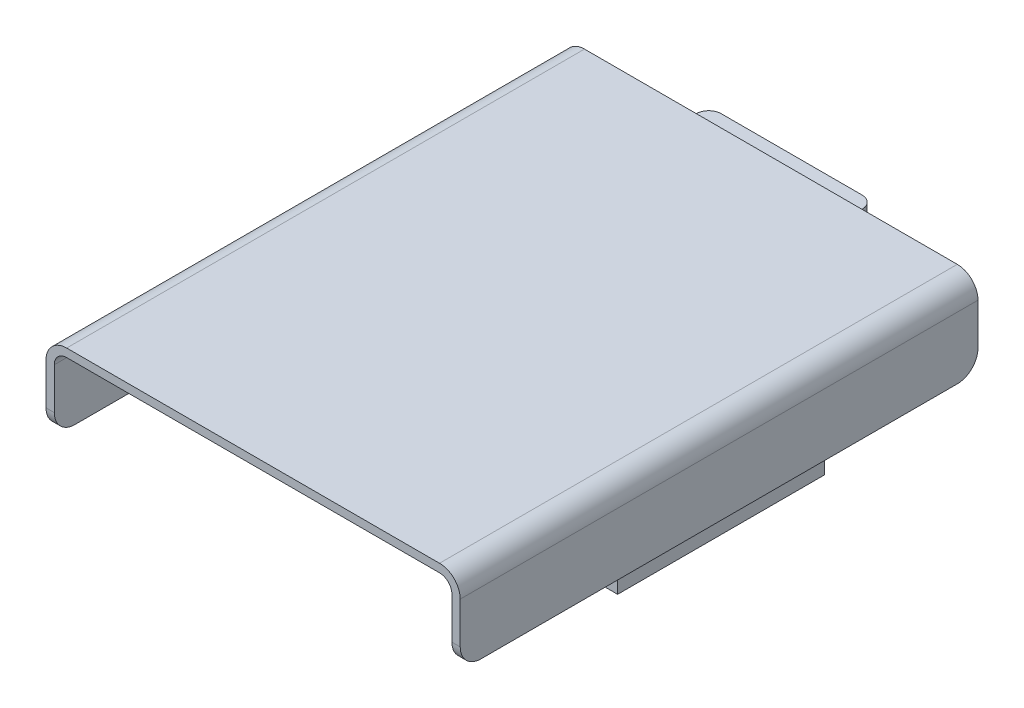
SolidWorks part; units mm, degrees
material "ABS"
ref_plane "Front Plane" through (0, 0, 0) normal (0, 0, 1) x (1, 0, 0)
ref_plane "Top Plane" through (0, 0, 0) normal (0, 1, 0) x (1, 0, 0)
ref_plane "Right Plane" through (0, 0, 0) normal (1, 0, 0) x (0, 0, -1)
sketch "Sketch1" plane through (0, 0, 0) normal (0, 0, 1) x (1, 0, 0)
  line L0 (-62.3906, 20.6479) -> (-62.3906, 26.5485) construction
  line L1 (-62.3906, 20.6479) -> (-62.3906, -14.3521) construction
  line L2 (-14.3906, 5.6479) -> (-14.3906, 20.6479)
  line L4 (-17.3906, 23.6479) -> (-107.3906, 23.6479)
  line L5 (-110.3906, 20.6479) -> (-110.3906, 5.6479)
  line L6 (-110.3906, 5.6479) -> (-112.3906, 5.6479)
  line L7 (-14.3906, 5.6479) -> (-12.3906, 5.6479)
  line L16 (-17.3906, 25.6479) -> (-107.3906, 25.6479)
  line L17 (-112.3906, 20.6479) -> (-112.3906, 5.6479)
  line L23 (-12.3906, 5.6479) -> (-12.3906, 20.6479)
  arc A0 (-107.3906, 25.6479) -> (-112.3906, 20.6479) centre (-107.3906, 20.6479) ccw
  arc A1 (-17.3906, 25.6479) -> (-12.3906, 20.6479) centre (-17.3906, 20.6479) cw
  arc A2 (-17.3906, 23.6479) -> (-14.3906, 20.6479) centre (-17.3906, 20.6479) cw
  arc A3 (-107.3906, 23.6479) -> (-110.3906, 20.6479) centre (-107.3906, 20.6479) ccw
  dimension "D4" = 20
  dimension "D5" = 100
  dimension "D1" = 5
  dimension "D2" = 2
  dimension "D3" = 20
extrude "Boss-Extrude1" add sketch "Sketch1" along normal blind 125
fillet "Fillet1" radius 5 4 edges at (-13.3906, 5.6479, 125) (-13.3906, 5.6479, 0) (-111.3906, 5.6479, 0) (-111.3906, 5.6479, 125)
sketch "Sketch2" plane through (0, 5.6479, 0) normal (0, -1, 0) x (1, 0, 0)
  line L1 (-107.3906, 35) -> (-110.3906, 35)
  line L2 (-107.3906, 35) -> (-107.3906, 85)
  line L3 (-107.3906, 85) -> (-110.3906, 85)
  line L4 (-110.3906, 35) -> (-110.3906, 85)
  line L6 (-82.3535, 85) -> (-110.3906, 85) construction
  line L7 (-110.3906, 120) -> (-110.3906, 5) construction
  line L9 (-12.3906, 35) -> (-12.3906, 85) construction
  line L10 (-15.3906, 85) -> (-12.3906, 85) construction
  line L11 (-15.3906, 35) -> (-15.3906, 85) construction
  line L12 (-15.3906, 35) -> (-12.3906, 35) construction
  point P5 (0, 0)
extrude "Boss-Extrude2" add sketch "Sketch2" against normal up to surface and the other way blind 5 up to face at (-109.2012, 22.4586, 62.5)
sketch "Sketch12" plane through (0, 5.6479, 0) normal (0, -1, 0) x (1, 0, 0)
  line L0 (-62.3906, 125) -> (-62.3906, 0) construction
  line L1 (-107.3906, 125) -> (-17.3906, 125) construction
  line L2 (-107.3906, 0) -> (-17.3906, 0) construction
  line L3 (-14.3906, 35) -> (-17.3906, 35)
  line L4 (-107.3906, 35) -> (-107.3906, 85)
  line L5 (-107.3906, 85) -> (-110.3906, 85)
  line L6 (-110.3906, 85) -> (-110.3906, 35)
  line L7 (-110.3906, 35) -> (-107.3906, 35)
  line L8 (-107.3906, 35) -> (-107.3906, 85) construction
  line L9 (-107.3906, 85) -> (-110.3906, 85) construction
  line L10 (-110.3906, 85) -> (-110.3906, 35) construction
  line L11 (-110.3906, 35) -> (-107.3906, 35) construction
  line L12 (-14.3906, 85) -> (-14.3906, 35)
  line L13 (-17.3906, 85) -> (-14.3906, 85)
  line L14 (-17.3906, 35) -> (-17.3906, 85)
  dimension "D1" = 0
extrude "Boss-Extrude5" add sketch "Sketch12" against normal up to surface and the other way blind 5 up to face at (-15.5799, 22.4586, 62.5)
sketch "Sketch3" plane through (0, 23.6479, 0) normal (0, -1, 0) x (1, 0, 0)
  line L0 (-62.3906, 0) -> (-62.3906, 120) construction
  line L1 (-42.3906, 10) -> (-82.3906, 10)
  line L2 (-42.3906, 10) -> (-42.3906, -5)
  line L3 (-42.3906, -5) -> (-82.3906, -5)
  line L4 (-82.3906, 10) -> (-82.3906, -5)
  line L5 (-62.3906, 125) -> (-62.3906, 127.9312) construction
  line L6 (-12.3906, 0) -> (-12.3906, 5) construction
  line L7 (-107.3906, 125) -> (-17.3906, 125) construction
  dimension "D1" = 20
  dimension "D2" = 40
  dimension "D3" = 15
  dimension "D4" = 50
extrude "Boss-Extrude3" add sketch "Sketch3" along normal blind 3
chamfer "Chamfer1" distance 4 angle 45 1 edges at (-62.3906, 23.6479, 10)
fillet "Fillet3" radius 4 2 edges at (-62.3906, 20.6479, 11) (-62.3906, 23.6479, 14)
fillet "Fillet4" radius 3 2 edges at (-82.3906, 22.1479, -5) (-42.3906, 22.1479, -5)
